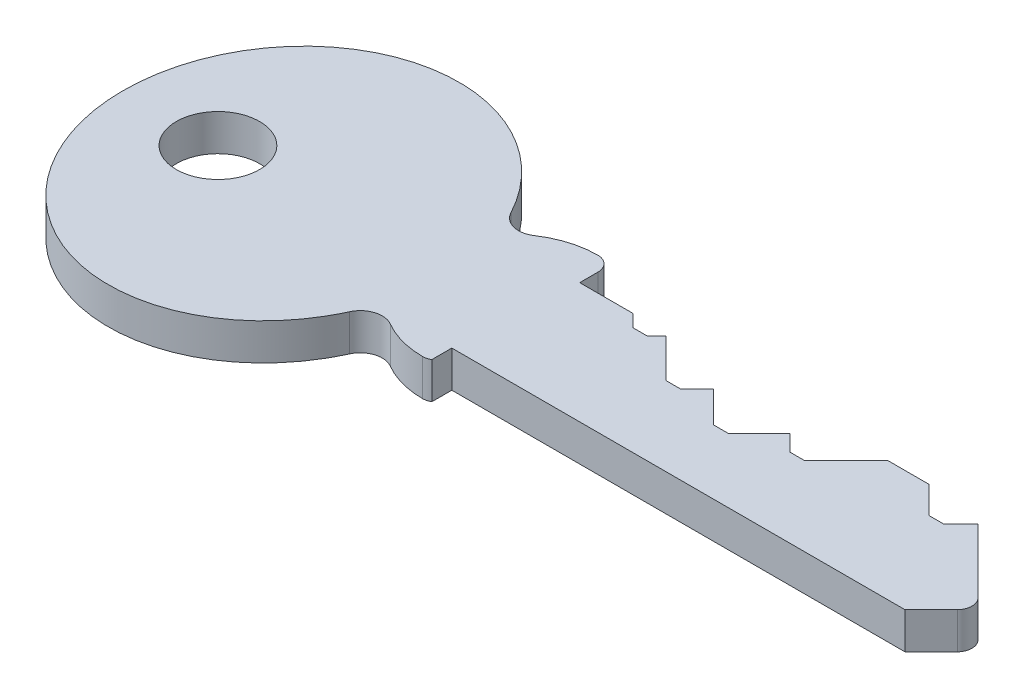
SolidWorks part; units mm, degrees
ref_plane "Front Plane" through (0, 0, 0) normal (0, 0, 1) x (1, 0, 0)
ref_plane "Top Plane" through (0, 0, 0) normal (0, 1, 0) x (1, 0, 0)
ref_plane "Right Plane" through (0, 0, 0) normal (1, 0, 0) x (0, 0, -1)
sketch "Sketch1" plane through (0, 0, 0) normal (0, 1, 0) x (1, 0, 0)
  line L0 (0, -4) -> (30.5, -4)
  line L1 (30.5, -4) -> (33, -1.5)
  line L2 (33, -1.5) -> (27.25, 4.25)
  line L3 (27.25, 4.25) -> (0, 4.25)
  line L4 (0, 4.25) -> (0, 5.5)
  line L5 (0, -4) -> (0, -4.5)
  line L7 (-1, 6.5) -> (-1, -5.5) construction
  arc A0 (0, 5.5) -> (-1, 6.5) centre (-1, 5.5) ccw
  arc A1 (-1, 6.5) -> (-4.3331, 5.489) centre (-1, 0.5) ccw
  arc A2 (-4.3331, 5.489) -> (-6.4901, 6.0309) centre (-5.1663, 6.7363) cw
  arc A3 (0, -4.5) -> (-1, -5.5) centre (-1, -4.5) cw
  arc A4 (-1, -5.5) -> (-4.0312, -4.678) centre (-1, 0.5) cw
  arc A5 (-4.0312, -4.678) -> (-6.1535, -5.3496) centre (-4.789, -5.9725) ccw
  circle A6 centre (-20.5, 0) radius 2.85
  ellipse E0 centre (-16, 0) end of major axis (-16, -12) minor radius 11 (-6.4901, 6.0309) -> (-6.1535, -5.3496) ccw
  point P21 (-1, 0.5)
  point P30 (7.4642, -5.8)
  dimension "D5" = 6.5
  dimension "D8" = 1.5
  dimension "D11" = 1
  dimension "D12" = 1
  dimension "D13" = 2.5
  dimension "D9" = 6
  dimension "D10" = 6
  dimension "D7" = 60
  dimension "D15" = 5.7
  dimension "D16" = 6.5
  dimension "D17" = 1.5
  dimension "D18" = 1.5
  dimension "D1" = 27
  dimension "D2" = 24
  dimension "D3" = 22
  dimension "D4" = 8.25
  dimension "D6" = 0.5
  dimension "D14" = 45
extrude "main body" add sketch "Sketch1" along normal mid plane 2.5
sketch "Sketch8" plane through (0, 1.25, 0) normal (0, 1, 0) x (1, 0, 0)
  line L1 (0, -4) -> (-0.5, -4)
  line L2 (0, -4) -> (0, -6)
  line L3 (0, -6) -> (-0.5, -6)
  line L4 (-0.5, -4) -> (-0.5, -6)
  dimension "D1" = 0.5
  dimension "D2" = 2
extrude "Cut-Extrude1" cut sketch "Sketch8" against normal blind 10
sketch "Sketch2" plane through (0, 0, 0) normal (0, 1, 0) x (1, 0, 0)
  line L0 (1, 13.4) -> (1, 6.9)
  line L1 (1, 6.9) -> (4.5, 3.4)
  line L2 (4.5, 3.4) -> (5.5, 3.4)
  line L3 (5.5, 3.4) -> (9, 6.9)
  line L4 (9, 6.9) -> (9, 13.4)
  line L5 (9, 13.4) -> (1, 13.4)
  line L6 (5, 3.4) -> (5, 13.4) construction
  line L10 (-0.5, -4) -> (30.5, -4) construction
  dimension "D1" = 1
  dimension "D2" = 45
  dimension "D3" = 5
  dimension "D4" = 10
  dimension "D5" = 8
  dimension "D6" = 7.4
extrude "cut 1" add sketch "Sketch2" along normal mid plane 2.5 separate body
sketch "Sketch3" plane through (0, 0, 0) normal (0, 1, 0) x (1, 0, 0)
  line L0 (5.25, 11.4) -> (5.25, 4.9)
  line L1 (5.25, 4.9) -> (8.75, 1.4)
  line L2 (8.75, 1.4) -> (9.75, 1.4)
  line L3 (9.75, 1.4) -> (13.25, 4.9)
  line L4 (13.25, 4.9) -> (13.25, 11.4)
  line L5 (13.25, 11.4) -> (5.25, 11.4)
  line L6 (9.25, 1.4) -> (9.25, 11.4) construction
  line L7 (-0.5, -4) -> (30.5, -4) construction
  dimension "D1" = 1
  dimension "D2" = 45
  dimension "D3" = 9.25
  dimension "D4" = 10
  dimension "D5" = 8
  dimension "D6" = 5.4
extrude "cut 2" add sketch "Sketch3" along normal mid plane 2.5 separate body
sketch "Sketch4" plane through (0, 0, 0) normal (0, 1, 0) x (1, 0, 0)
  line L0 (9.5, 10.4) -> (9.5, 3.9)
  line L1 (9.5, 3.9) -> (13, 0.4)
  line L2 (13, 0.4) -> (14, 0.4)
  line L3 (14, 0.4) -> (17.5, 3.9)
  line L4 (17.5, 3.9) -> (17.5, 10.4)
  line L5 (17.5, 10.4) -> (9.5, 10.4)
  line L6 (13.5, 0.4) -> (13.5, 10.4) construction
  line L7 (-0.5, -4) -> (30.5, -4) construction
  dimension "D1" = 1
  dimension "D2" = 45
  dimension "D3" = 13.5
  dimension "D4" = 10
  dimension "D5" = 8
  dimension "D6" = 4.4
extrude "cut 3" add sketch "Sketch4" along normal mid plane 2.5 separate body
sketch "Sketch5" plane through (0, 0, 0) normal (0, 1, 0) x (1, 0, 0)
  line L0 (13.75, 11.4) -> (13.75, 4.9)
  line L1 (13.75, 4.9) -> (17.25, 1.4)
  line L2 (17.25, 1.4) -> (18.25, 1.4)
  line L3 (18.25, 1.4) -> (21.75, 4.9)
  line L4 (21.75, 4.9) -> (21.75, 11.4)
  line L5 (21.75, 11.4) -> (13.75, 11.4)
  line L6 (17.75, 1.4) -> (17.75, 11.4) construction
  line L7 (-0.5, -4) -> (30.5, -4) construction
  dimension "D1" = 1
  dimension "D2" = 45
  dimension "D3" = 17.75
  dimension "D4" = 10
  dimension "D5" = 8
  dimension "D6" = 5.4
extrude "cut 4" add sketch "Sketch5" along normal mid plane 2.5 separate body
sketch "Sketch6" plane through (0, 0, 0) normal (0, 1, 0) x (1, 0, 0)
  line L0 (18, 14.25) -> (18, 7.75)
  line L1 (18, 7.75) -> (21.5, 4.25)
  line L2 (21.5, 4.25) -> (22.5, 4.25)
  line L3 (22.5, 4.25) -> (26, 7.75)
  line L4 (26, 7.75) -> (26, 14.25)
  line L5 (26, 14.25) -> (18, 14.25)
  line L6 (22, 4.25) -> (22, 14.25) construction
  line L8 (-0.5, -4) -> (30.5, -4) construction
  dimension "D1" = 1
  dimension "D2" = 45
  dimension "D3" = 22
  dimension "D4" = 10
  dimension "D5" = 8
  dimension "D6" = 8.25
extrude "cut 5" add sketch "Sketch6" along normal mid plane 2.5 separate body
sketch "Sketch7" plane through (0, 0, 0) normal (0, 1, 0) x (1, 0, 0)
  line L0 (22.25, 12.4) -> (22.25, 5.9)
  line L1 (22.25, 5.9) -> (25.75, 2.4)
  line L2 (25.75, 2.4) -> (26.75, 2.4)
  line L3 (26.75, 2.4) -> (30.25, 5.9)
  line L4 (30.25, 5.9) -> (30.25, 12.4)
  line L5 (30.25, 12.4) -> (22.25, 12.4)
  line L6 (26.25, 2.4) -> (26.25, 12.4) construction
  line L7 (-0.5, -4) -> (30.5, -4) construction
  dimension "D1" = 1
  dimension "D2" = 45
  dimension "D3" = 26.25
  dimension "D4" = 10
  dimension "D5" = 8
  dimension "D6" = 6.4
extrude "cut 6" add sketch "Sketch7" along normal mid plane 2.5 separate body
combine bodies "Combine1" operation type subtract main body 109 bodies to subtract 102 103 104 105 106 107
fillet "Fillet1" radius 1 1 edges at (33, 0, 1.5)
